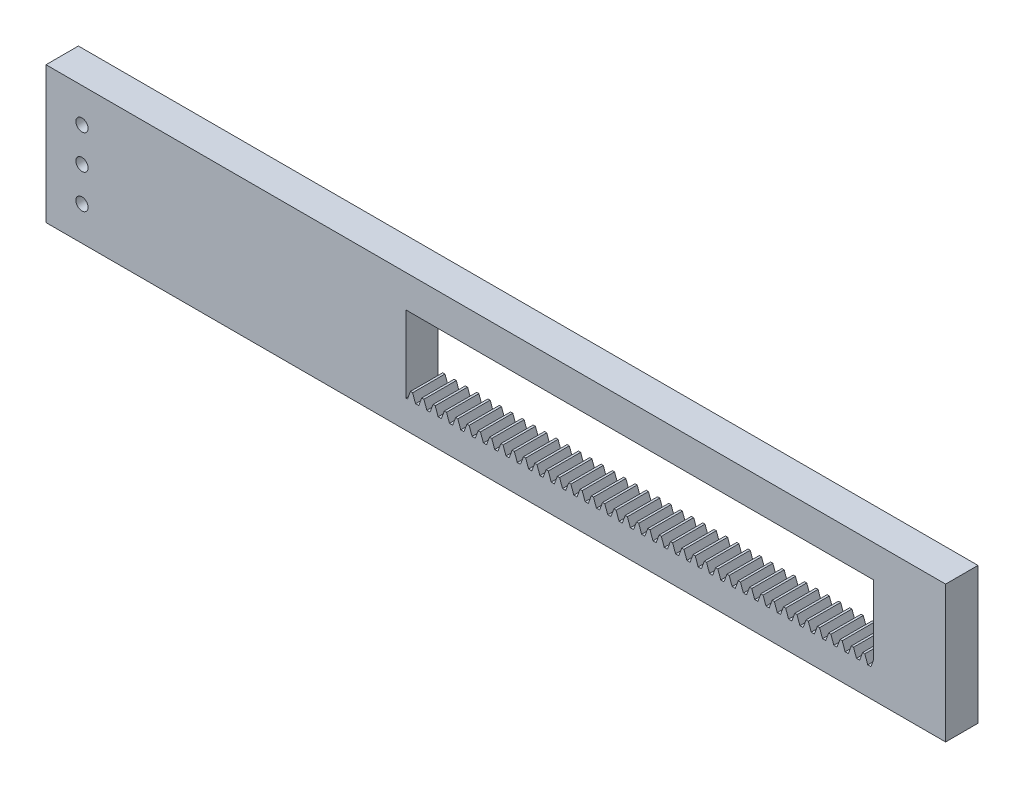
SolidWorks part; units mm, degrees
extrude "Blank" add sketch "BlankSke" against normal blind 9
sketch "BlankSke" plane through (0, 0, 0) normal (0, 0, 1) x (1, 0, 0)
  line L1 (0, 0) -> (130, 0)
  line L2 (0, 0) -> (0, 10)
  line L3 (0, 10) -> (130, 10)
  line L4 (130, 0) -> (130, 10)
  dimension "Length" = 130
ref_plane "Plane1" through (0, 0, 0) normal (0, 0, 1) x (1, 0, 0)
ref_plane "Plane2" through (0, 0, 0) normal (0, 1, 0) x (1, 0, 0)
ref_plane "Plane3" through (0, 0, 0) normal (1, 0, 0) x (0, 0, -1)
sketch "HoldingSke" plane through (0, 0, 0) normal (0, 1, 0) x (1, 0, 0)
  line L0 (0, 0) -> (0.1392, 0.9903)
  line L1 (-15, 0) -> (100, 0) construction
  line L2 (0, 0) -> (-2.1039, 2.3779)
  line L3 (0, 0) -> (-11.863, 4.5341)
  line L4 (0, 0) -> (-0.1507, 8.6347)
  line L5 (0, 0) -> (-23.7986, -8.8762)
  line L6 (0, 0) -> (-10.5278, -7.1032)
  line L9 (-71.009, 38.7566) -> (192.105, 134.5223)
  line L10 (-76.2, 3.3779) -> (-67.2, 3.3779)
  line L11 (0, 0) -> (-9, 0)
  line L12 (-76.2, 101.6) -> (-76.162, 101.6)
  line L13 (24.9733, 27.94) -> (52.9518, 28.4284)
  line L14 (24.9733, 27.94) -> (24.9743, 27.94)
  line L15 (24.9733, 27.94) -> (100.4006, 29.5858)
  circle A0 centre (0, 0) radius 19.05
  circle A1 centre (0, 0) radius 4.5
  circle A2 centre (0, 0) radius 12.7
  dimension "Num_teeth" = 91
  dimension "Width" = 9
  dimension "Pitch_height" = 9
sketch "TooCutSkeIll" plane through (0, 0, 0) normal (0, 0, 1) x (1, 0, 0)
  line L0 (-1.2538, 9.9737) -> (-0.5045, 7.9152)
  line L1 (-0.2687, 7.75) -> (0.2687, 7.75)
  line L2 (0.5045, 7.9152) -> (1.2538, 9.9737)
  line L3 (130, 10) -> (0, 10) construction
  line L4 (0, 0) -> (0, 64.897) construction
  line L5 (-13.208, 9) -> (12.954, 9) construction
  line L6 (0, 0) -> (130, 0) construction
  line L7 (0.8994, 9) -> (0.8994, 48.7463) construction
  line L8 (-0.8994, 9) -> (-0.8994, 48.7463) construction
  line L9 (1.2914, 10) -> (1.2914, 10.0254)
  line L10 (-1.2914, 10) -> (-1.2914, 10.0254)
  line L11 (-1.2914, 10.0254) -> (1.2914, 10.0254)
  arc A0 (0.2687, 7.75) -> (0.5045, 7.9152) centre (0.2687, 8.001) ccw
  arc A1 (-0.5045, 7.9152) -> (-0.2687, 7.75) centre (-0.2687, 8.001) ccw
  arc A2 (1.2914, 10) -> (1.2538, 9.9737) centre (1.2914, 9.96) ccw
  arc A3 (-1.2538, 9.9737) -> (-1.2914, 10) centre (-1.2914, 9.96) ccw
  dimension "Addendum_plus" = 1.0254
  dimension "Pitch_height" = 9
  dimension "Pressure_angle" = 20
  dimension "Gap_width" = 1.7988
  dimension "Dedendum" = 1.25
extrude "ToothCutIll" [suppressed] cut sketch "TooCutSkeIll" against normal through all
sketch "TooCutSkeSim" plane through (0, 0, 0) normal (0, 0, 1) x (1, 0, 0)
  line L0 (0.4444, 7.75) -> (-0.4444, 7.75)
  line L1 (1.2726, 10.0254) -> (0.4444, 7.75)
  line L2 (0, 17.4625) -> (0, 53.467) construction
  line L3 (1.2726, 10.0254) -> (-1.2726, 10.0254)
  line L6 (-1.2726, 10.0254) -> (-0.4444, 7.75)
  line L9 (-0.8994, 9) -> (0.8994, 9) construction
  line L10 (0, 0) -> (130, 0) construction
  line L11 (0.8994, 9) -> (0.8994, 53.467) construction
  line L12 (-0.8994, 9) -> (-0.8994, 53.467) construction
  dimension "Addendum_plus" = 1.0254
  dimension "Pitch_height" = 9
  dimension "Pressure_angle" = 20
  dimension "Gap_width" = 1.7988
  dimension "Dedendum" = 1.25
extrude "ToothCutSim" cut sketch "TooCutSkeSim" against normal through all
pattern_linear "TeethCuts" count 91 spacing 3.1416 along (1, 0, 0) of "ToothCutIll", "ToothCutSim"
sketch "Sketch2" plane through (0, 0, 0) normal (0, -1, 0) x (1, 0, 0)
  line L1 (130, -9) -> (150, -9)
  line L2 (130, -9) -> (130, 0)
  line L3 (130, 0) -> (150, 0)
  line L4 (150, -9) -> (150, 0)
  dimension "D1" = 20
extrude "Boss-Extrude1" add sketch "Sketch2" against normal blind 29
sketch "Sketch3" plane through (130, 0, 0) normal (-1, 0, 0) x (0, 0, 1)
  line L1 (-9, 29) -> (0, 29)
  line L2 (-9, 29) -> (-9, 38)
  line L3 (-9, 38) -> (0, 38)
  line L4 (0, 29) -> (0, 38)
  dimension "D1" = 9
extrude "Boss-Extrude2" add sketch "Sketch3" against normal blind 20
extrude "Boss-Extrude3" add sketch "Sketch3<2>" along normal blind 130
sketch "Sketch3<2>" plane through (130, 0, 0) normal (-1, 0, 0) x (0, 0, 1) same geometry as "Sketch3"
sketch "Sketch4" plane through (0, 0, 0) normal (-1, 0, 0) x (0, 0, 1)
  line L1 (-9, 38) -> (0, 38)
  line L2 (-9, 38) -> (-9, 0)
  line L3 (-9, 0) -> (0, 0)
  line L4 (0, 38) -> (0, 0)
extrude "Boss-Extrude4" add sketch "Sketch4" along normal blind 100
sketch "Sketch5" plane through (0, 0, -9) normal (0, 0, -1) x (-1, 0, 0)
  line L0 (100, 38) -> (100, 0) construction
  line L2 (100, 19) -> (100, 0)
  line L3 (100.362, 19) -> (93.6419, 19)
  circle A0 centre (90, 19) radius 1.7
  circle A1 centre (90, 9.5) radius 1.7
  circle A2 centre (90, 28.5) radius 1.7
  point P4 (100, 19)
  point P7 (100, 9.5)
  dimension "D1" = 3.4
  dimension "D3" = 3.4
  dimension "D2" = 10
extrude "Cut-Extrude1" cut sketch "Sketch5" against normal blind 10 contours A2 | A0 | A1 region at (-90, 19, -9) region at (-90, 9.5, -9) region at (-90, 28.5, -9)
equation "' \"Module@HoldingSke\" = 6.35"
equation "' \"Num_teeth@HoldingSke\" = 12"
equation "' \"Ap@HoldingSke\" =  20"
equation "' \"Ap@HoldingSke\" = 20"
equation "' \"Width@HoldingSke\" = 0.25 * 25.4"
equation "' \"Show_teeth@HoldingSke\" = 500"
equation "' \"Backlash@HoldingSke\" = 0.009 * 25.4"
equation "' \"Addendum_fac@HoldingSke\" = 1.0"
equation "' \"Dedendum_fac@HoldingSke\" = 1.25"
equation "' \"Dedendum_add@HoldingSke\" = 0.00005 * 25.4"
equation "' \"Clearance_fac@HoldingSke\" = 0.25"
equation "' \"Pitch_height@HoldingSke\" = 1 * 25.4"
equation "' \"Length@HoldingSke\" = 4.71 * 25.4"
equation "\"Pitch@HoldingSke\" = 1 / \"Module@HoldingSke\""
equation "\"MPH@HoldingSke\" = \"Dedendum_fac@HoldingSke\" / \"Pitch@HoldingSke\" + 2 * \"Dedendum_add@HoldingSke\" + 0.002 * 25.4"
equation "\"MPH@HoldingSke\" = ((sgn( \"MPH@HoldingSke\" - \"Pitch_height@HoldingSke\")+1)*( \"MPH@HoldingSke\" - \"Pitch_height@HoldingSke\"))/2 + \"Pitch_height@HoldingSke\""
equation "\"Blank_height@BlankSke\" = \"Pitch_height@HoldingSke\" + \"Addendum_fac@HoldingSke\"  / \"Pitch@HoldingSke\" "
equation "\"Length@BlankSke\" = 130"
equation "\"Face_width@Blank\" = \"Width@HoldingSke\""
equation "\"Pressure_angle@TooCutSkeIll\" = \"Ap@HoldingSke\""
equation "\"Addendum_plus@TooCutSkeIll\" =  \"Addendum_fac@HoldingSke\"  / \"Pitch@HoldingSke\" + 0.001 *25.4"
equation "\"Dedendum@TooCutSkeIll\" = \"Dedendum_fac@HoldingSke\"  / \"Pitch@HoldingSke\""
equation "\"Pitch_height@TooCutSkeIll\" =  \"MPH@HoldingSke\""
equation "\"Gap_width@TooCutSkeIll\" = 3.14159265 / 2 / \"Pitch@HoldingSke\" + 6 * \"Backlash@HoldingSke\""
equation "\"Pressure_angle@TooCutSkeSim\" = \"Ap@HoldingSke\""
equation "\"Addendum_plus@TooCutSkeSim\" =  \"Addendum_fac@HoldingSke\"  / \"Pitch@HoldingSke\" + 0.001 * 25.4"
equation "\"Dedendum@TooCutSkeSim\" = \"Dedendum_fac@HoldingSke\"  / \"Pitch@HoldingSke\""
equation "\"Pitch_height@TooCutSkeSim\" =  \"MPH@HoldingSke\""
equation "\"Gap_width@TooCutSkeSim\" = 3.14159265 / 2 / \"Pitch@HoldingSke\" + 6 * \"Backlash@HoldingSke\""
equation "\"Root_fillet@TooCutSkeIll\" = \"Clearance_fac@HoldingSke\" / \"Pitch@HoldingSke\" + \"Dedendum_add@HoldingSke\""
equation "\"Break_rad@TooCutSkeIll\" = 0.02 / \"Pitch@HoldingSke\" * 2"
equation "\"Linear_pitch@TeethCuts\" = 3.14159265 / \"Pitch@HoldingSke\""
equation "\"Num_teeth@HoldingSke\" = int( ( \"Length@HoldingSke\" + 0 ) / (3.14159265 / \"Pitch@HoldingSke\")) + 0.9999  + 1"
equation " \"Num_teeth@TeethCuts\" = int( \"Show_teeth@HoldingSke\" ) + 1"
equation " \"Num_teeth@TeethCuts\" = ((sgn( \"Num_teeth@TeethCuts\" - \"Num_teeth@HoldingSke\" )-1)*( \"Num_teeth@TeethCuts\" - \"Num_teeth@HoldingSke\" ))/-2+ \"Num_teeth@HoldingSke\""
equation " \"Num_teeth@TeethCuts\" = ((sgn( \"Num_teeth@TeethCuts\" - 2.0)+1)*( \"Num_teeth@TeethCuts\" - 2.0))/2 +2.0"
